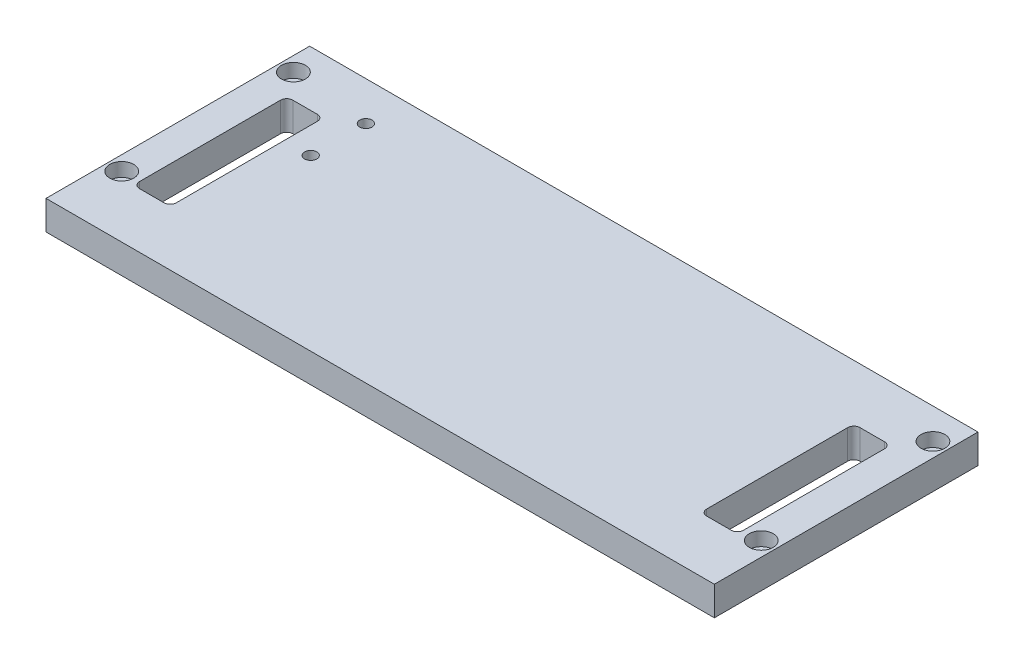
SolidWorks part; units mm, degrees
ref_plane "前视基准面" through (0, 0, 0) normal (0, 0, 1) x (1, 0, 0)
ref_plane "上视基准面" through (0, 0, 0) normal (0, 1, 0) x (1, 0, 0)
ref_plane "右视基准面" through (0, 0, 0) normal (1, 0, 0) x (0, 0, -1)
sketch "草图1" plane through (0, 0, 0) normal (0, 1, 0) x (1, 0, 0)
  line L1 (-109, 43) -> (109, 43)
  line L2 (-109, 43) -> (-109, -43)
  line L3 (-109, -43) -> (109, -43)
  line L4 (109, 43) -> (109, -43)
  line L5 (-109, 43) -> (109, -43) construction
  line L6 (-109, -43) -> (109, 43) construction
  point P0 (0, 0)
  dimension "D1" = 218
  dimension "D2" = 86
extrude "凸台-拉伸1" add sketch "草图1" along normal blind 9.5
sketch "草图2" plane through (0, 9.5, 0) normal (0, 1, 0) x (1, 0, 0)
  line L0 (-109, 43) -> (-109, -43) construction
  line L1 (-86.5, -25) -> (-98.5, -25)
  line L2 (-86.5, -25) -> (-86.5, 25)
  line L3 (-86.5, 25) -> (-98.5, 25)
  line L4 (-98.5, -25) -> (-98.5, 25)
  line L5 (-86.5, -25) -> (-98.5, 25) construction
  line L6 (-86.5, 25) -> (-98.5, -25) construction
  line L12 (109, 43) -> (-109, 43) construction
  line L13 (0, -43) -> (0, 43) construction
  line L15 (-109, -43) -> (109, -43) construction
  point P0 (-92.5, 0)
  dimension "D1" = 12
  dimension "D2" = 50
  dimension "D3" = 10.5
  dimension "D7" = 18
extrude "切除-拉伸1" cut sketch "草图2" against normal through all
fillet "圆角1" radius 2 4 edges at (-98.5, 4.75, -25) (-86.5, 4.75, -25) (-86.5, 4.75, 25) (-98.5, 4.75, 25)
ref_plane "基准面1" through (0, 0, 0) normal (1, 0, 0) x (0, 0, -1)
mirror "镜向3" about plane through (0, 0, 0) normal (1, 0, 0) of "切除-拉伸1"
fillet "圆角2" radius 2 4 edges at (86.5, 4.75, -25) (98.5, 4.75, -25) (98.5, 4.75, 25) (86.5, 4.75, 25)
sketch "草图4" plane through (0, 0, 0) normal (0, -1, 0) x (1, 0, 0)
  line L0 (109, 43) -> (109, -43) construction
  line L1 (-109, 43) -> (109, 43) construction
  line L2 (109, -43) -> (-109, -43) construction
  circle A0 centre (104.3, 23) radius 1.95
  circle A1 centre (104.3, -33) radius 1.95
  dimension "D1" = 3.9
  dimension "D2" = 4.7
  dimension "D3" = 4.7
  dimension "D4" = 20
  dimension "D5" = 10
extrude "切除-拉伸3" cut sketch "草图4" against normal through all
mirror "镜向4" about plane through (0, 0, 0) normal (1, 0, 0) of "切除-拉伸3"
sketch "草图5" plane through (0, 9.5, 0) normal (0, 1, 0) x (1, 0, 0)
  circle A0 centre (104.3, -23) radius 3.9
  circle A1 centre (104.3, 33) radius 3.9
  circle A2 centre (-104.3, -23) radius 3.9
  circle A3 centre (-104.3, 33) radius 3.9
  dimension "D1" = 7.8
extrude "切除-拉伸4" cut sketch "草图5" against normal blind 4.5
sketch "草图8" plane through (0, 0, 0) normal (0, -1, 0) x (1, 0, 0)
  circle A0 centre (-77.957, -12.3) radius 2
  circle A1 centre (-77.957, -30.3) radius 2
  dimension "D1" = 4
extrude "切除-拉伸6" cut sketch "草图8" against normal through all
sketch "草图9" plane through (0, 0, 0) normal (0, -1, 0) x (1, 0, 0)
  circle A0 centre (-77.957, -12.3) radius 4
  circle A1 centre (-77.957, -30.3) radius 4
  dimension "D1" = 8
extrude "切除-拉伸7" cut sketch "草图9" against normal blind 4.5
